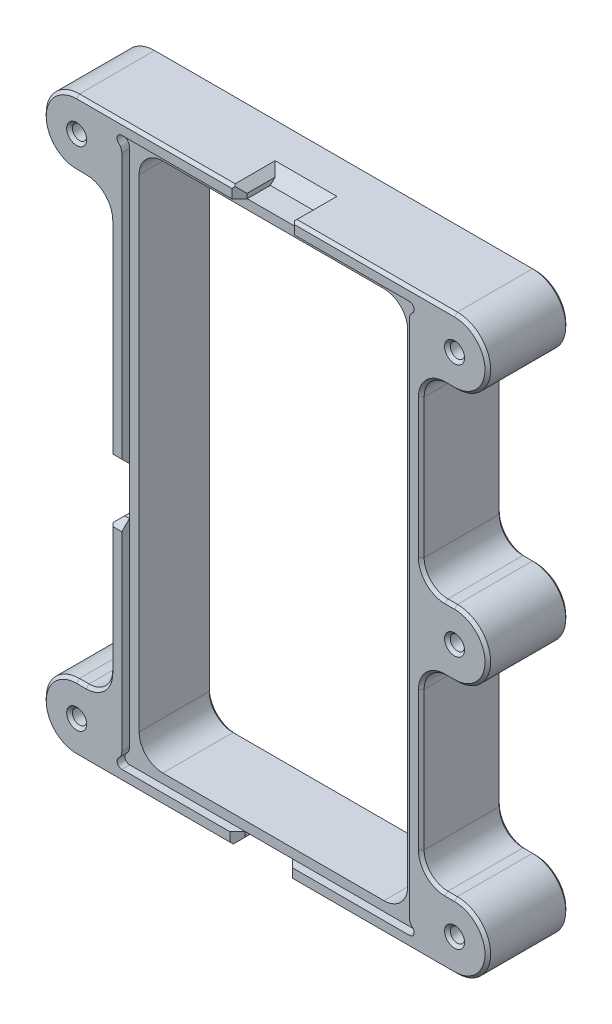
SolidWorks part; units mm, degrees
ref_plane "Top Plane" through (0, 0, 0) normal (0, 0, 1) x (1, 0, 0)
ref_plane "Right Plane" through (0, 0, 0) normal (0, 1, 0) x (1, 0, 0)
ref_plane "Front Plane" through (0, 0, 0) normal (1, 0, 0) x (0, 0, -1)
ref_plane "Plane1" through (60, 0, 0.0102) normal (0, 1, 0) x (1, 0, 0)
sketch "Sketch2" plane through (0, 0, 0) normal (0, 0, 1) x (1, 0, 0)
  line L4 (62.75, 2.75) -> (-2.75, 2.75)
  line L5 (-2.75, -11.25) -> (-2.75, -103.75)
  line L6 (-2.75, -117.75) -> (62.75, -117.75)
  line L8 (-0.25, -115.25) -> (60.25, -115.25)
  line L9 (60.25, -115.25) -> (60.25, 0.25)
  line L10 (-0.25, 0.25) -> (-0.25, -115.25)
  line L11 (60.25, 0.25) -> (-0.25, 0.25)
  line L12 (-0.25, -115.25) -> (60.25, -115.25)
  line L13 (60.25, -115.25) -> (60.25, 0.25)
  line L14 (-0.25, 0.25) -> (-0.25, -115.25)
  line L15 (60.25, 0.25) -> (-0.25, 0.25)
  line L16 (-2.75, -57.5) -> (62.75, -57.5) construction
  line L17 (30, -117.75) -> (30, 2.75) construction
  line L18 (-2.75, -117.75) -> (-9.75, -117.75)
  line L19 (-9.75, -103.75) -> (-2.75, -103.75)
  line L20 (-9.75, -11.25) -> (-2.75, -11.25)
  line L21 (-2.75, 2.75) -> (-9.75, 2.75)
  line L22 (-2.75, 2.75) -> (-2.75, -117.75) construction
  line L23 (62.75, -117.75) -> (62.75, 2.75) construction
  line L24 (62.75, 2.75) -> (69.75, 2.75)
  line L25 (69.75, -11.25) -> (62.75, -11.25)
  line L26 (69.75, -103.75) -> (62.75, -103.75)
  line L27 (62.75, -117.75) -> (69.75, -117.75)
  line L28 (62.75, -11.25) -> (62.75, -50.5)
  line L29 (69.75, -64.5) -> (62.75, -64.5)
  line L30 (69.75, -50.5) -> (62.75, -50.5)
  line L31 (62.75, -64.5) -> (62.75, -103.75)
  arc A0 (-9.75, -103.75) -> (-9.75, -117.75) centre (-9.75, -110.75) ccw
  circle A1 centre (-9.75, -110.75) radius 1.5
  circle A2 centre (-9.75, -4.25) radius 1.5
  arc A3 (-9.75, -11.25) -> (-9.75, 2.75) centre (-9.75, -4.25) cw
  arc A4 (69.75, -11.25) -> (69.75, 2.75) centre (69.75, -4.25) ccw
  circle A5 centre (69.75, -4.25) radius 1.5
  circle A6 centre (69.75, -110.75) radius 1.5
  arc A7 (69.75, -103.75) -> (69.75, -117.75) centre (69.75, -110.75) cw
  arc A8 (69.75, -64.5) -> (69.75, -50.5) centre (69.75, -57.5) ccw
  circle A9 centre (69.75, -57.5) radius 1.5
  dimension "D3" = 14
  dimension "D4" = 3
  dimension "D1" = 0.25
  dimension "D2" = 2.5
extrude "Boss-Extrude1" add sketch "Sketch2" against normal blind 17 contours L29 A8 L30 L28 L25 A4 L24 L4 L21 A3 L20 L5 L19 A0 L18 L6 L27 A7 L26 L31 A9 A6 A5 L15 L13 L12 L14 A1 A2 region at (66.25, 1.2248, 0)
sketch "Sketch3" plane through (0, 0, -17) normal (0, 0, -1) x (-1, 0, 0)
  line L8 (-1.75, -113.25) -> (-1.75, -1.75)
  line L9 (-1.75, -1.75) -> (-58.25, -1.75)
  line L10 (-58.25, -113.25) -> (-1.75, -113.25)
  line L11 (-58.25, -1.75) -> (-58.25, -113.25)
  line L12 (-1.75, -113.25) -> (-1.75, -1.75)
  line L13 (-1.75, -1.75) -> (-58.25, -1.75)
  line L14 (-58.25, -113.25) -> (-1.75, -113.25)
  line L15 (-58.25, -1.75) -> (-58.25, -113.25)
  line M8 (-60.25, 0.25) -> (0.25, 0.25)
  line M9 (0.25, 0.25) -> (0.25, -115.25)
  line M10 (0.25, -115.25) -> (-60.25, -115.25)
  line M11 (-60.25, -115.25) -> (-60.25, 0.25)
  dimension "D1" = 2
extrude "Boss-Extrude2" add sketch "Sketch3" against normal up to surface (15.3597 mm away) contours L15 L13 L12 L14 M8 M11 M10 M9 region at (30, -1.0539, -17)
fillet "Fillet1" radius 5 4 edges at (1.75, -1.75, -9.3201) (58.25, -1.75, -9.3201) (1.75, -113.25, -9.3201) (58.25, -113.25, -9.3201)
fillet "Fillet2" radius 5 6 edges at (62.75, -50.5, -8.5) (62.75, -64.5, -8.5) (62.75, -103.75, -8.5) (62.75, -11.25, -8.5) (-2.75, -11.25, -8.5) (-2.75, -103.75, -8.5)
sketch "Sketch4" plane through (0, 0, 0) normal (0, 0, 1) x (1, 0, 0)
  line L0 (27.195, -107.298) -> (31.005, -107.298) construction
  line L1 (7.49, -67.267) -> (7.49, -63.457) construction
  line L2 (27.595, -7.802) -> (31.405, -7.802) construction
  line L3 (29.5, -7.802) -> (29.5, 0.25) construction
  line L4 (60.25, 0.25) -> (-0.25, 0.25) construction
  line L5 (29.1, -107.298) -> (29.1, -115.25) construction
  line L6 (-0.25, -115.25) -> (60.25, -115.25) construction
  line L7 (7.49, -65.362) -> (-0.25, -65.362) construction
  line L8 (-0.25, 0.25) -> (-0.25, -115.25) construction
  line L9 (69.75, -117.75) -> (-9.75, -117.75) construction
  line L10 (24.1, -115.25) -> (34.1, -115.25)
  line L11 (24.1, -115.25) -> (24.1, -117.75)
  line L12 (24.1, -117.75) -> (34.1, -117.75)
  line L13 (34.1, -115.25) -> (34.1, -117.75)
  line L14 (-2.75, -16.25) -> (-2.75, -98.75) construction
  line L15 (-2.75, -70.362) -> (-0.25, -70.362)
  line L16 (-2.75, -70.362) -> (-2.75, -60.362)
  line L17 (-2.75, -60.362) -> (-0.25, -60.362)
  line L18 (-0.25, -70.362) -> (-0.25, -60.362)
  line L19 (-9.75, 2.75) -> (69.75, 2.75) construction
  line L20 (24.5, 0.25) -> (34.5, 0.25)
  line L21 (24.5, 0.25) -> (24.5, 2.75)
  line L22 (24.5, 2.75) -> (34.5, 2.75)
  line L23 (34.5, 0.25) -> (34.5, 2.75)
  circle A0 centre (31.405, -7.802) radius 0.7 construction
  circle A1 centre (27.595, -7.802) radius 0.7 construction
  circle A2 centre (31.405, -7.802) radius 0.7
  circle A3 centre (27.595, -7.802) radius 0.7
  circle A4 centre (27.195, -107.298) radius 0.7 construction
  circle A5 centre (31.005, -107.298) radius 0.7 construction
  circle A6 centre (27.195, -107.298) radius 0.7
  circle A7 centre (31.005, -107.298) radius 0.7
  circle A8 centre (7.49, -67.267) radius 0.7 construction
  circle A9 centre (7.49, -63.457) radius 0.7 construction
  circle A10 centre (7.49, -67.267) radius 0.7
  circle A11 centre (7.49, -63.457) radius 0.7
  point P48 (0, 0)
  point P49 (0, 0)
  point P50 (0, 0)
  dimension "D1" = 10
extrude "Cut-Extrude1" cut sketch "Sketch4" against normal blind 6.5 contours L11 L10 L13 L12 | L16 L15 L18 L17 | L21 L20 L23 L22
chamfer "Chamfer1" distance 1.6 angle 45 6 edges at (24.5, 1.5, 0) (34.5, 1.5, 0) (-1.5, -60.362, 0) (-1.5, -70.362, 0) (34.1, -116.5, 0) (24.1, -116.5, 0)
chamfer "Chamfer2" distance 2.5 angle 45 3 edges at (29.5, 2.75, -6.5) (-2.75, -65.362, -6.5) (29.1, -117.75, -6.5)
sketch "Sketch5" plane through (0, 0, 0) normal (0, 0, 1) x (1, 0, 0)
  line L0 (-0.25, 0.25) -> (-0.25, -58.762) construction
  line L5 (-0.25, -71.962) -> (-0.25, -115.25) construction
  line L6 (60.25, -115.25) -> (60.25, 0.25) construction
  line L7 (60.25, 0.25) -> (36.1, 0.25) construction
  line L8 (-0.25, -115.25) -> (22.5, -115.25) construction
  circle A2 centre (-0.25, -0.75) radius 1
  circle A3 centre (-0.25, -114.25) radius 1
  circle A4 centre (60.25, -114.25) radius 1
  circle A5 centre (60.25, -0.75) radius 1
  point P16 (60.25, -2.3032)
  point P19 (-0.25, -112.0231)
  dimension "D1" = 2
extrude "Cut-Extrude2" cut sketch "Sketch5" against normal up to surface (1.6403 mm away) contours A3 | A4 | A5 | A2 up to face at (23.67, -59.0724, -1.6403)
fillet "Fillet3" radius 2 4 edges at (60.25, -113.25, -0.8201) (60.25, -1.75, -0.8201) (-0.25, -1.75, -0.8201) (-0.25, -113.25, -0.8201)
chamfer "Chamfer3" distance 0.6 angle 45 22 edges at (-16.75, -4.25, -17) (30, 2.75, -17) (-8.75, -11.25, -17) (76.75, -4.25, -17) (-4.2145, -12.7145, -17) (68.75, -11.25, -17) (-2.75, -57.5, -17) (64.2145, -12.7145, -17) (-4.2145, -102.2855, -17) (62.75, -30.875, -17) (-8.75, -103.75, -17) (64.2145, -49.0355, -17) (-16.75, -110.75, -17) (68.75, -50.5, -17) (30, -117.75, -17) (76.75, -57.5, -17) (76.75, -110.75, -17) (68.75, -64.5, -17) (68.75, -103.75, -17) (64.2145, -65.9645, -17) (64.2145, -102.2855, -17) (62.75, -84.125, -17)
chamfer "Chamfer4" distance 0.6 angle 45 25 edges at (6.575, 2.75, 0) (-16.75, -4.25, 0) (-8.75, -11.25, 0) (-4.2145, -12.7145, 0) (-2.75, -37.506, 0) (6.375, -117.75, 0) (-16.75, -110.75, 0) (-2.75, -85.356, 0) (-8.75, -103.75, 0) (-4.2145, -102.2855, 0) (52.925, 2.75, 0) (76.75, -4.25, 0) (68.75, -11.25, 0) (64.2145, -12.7145, 0) (62.75, -30.875, 0) (64.2145, -49.0355, 0) (68.75, -50.5, 0) (52.725, -117.75, 0) (76.75, -57.5, 0) (76.75, -110.75, 0) (68.75, -64.5, 0) (68.75, -103.75, 0) (64.2145, -65.9645, 0) (64.2145, -102.2855, 0) (62.75, -84.125, 0)
chamfer "Chamfer5" distance 1.5 angle 45 6 edges at (24.1, -117.75, -5.3) (34.1, -117.75, -5.3) (-2.75, -70.362, -5.3) (-2.75, -60.362, -5.3) (24.5, 2.75, -5.3) (34.5, 2.75, -5.3)
chamfer "Chamfer6" distance 0.6 angle 45 8 edges at (58.25, -57.5, -17) (56.7855, -111.7855, -17) (56.7855, -3.2145, -17) (30, -113.25, -17) (30, -1.75, -17) (3.2145, -111.7855, -17) (3.2145, -3.2145, -17) (1.75, -57.5, -17)
sketch "Sketch6" plane through (0, 0, -17) normal (0, 0, -1) x (-1, 0, 0)
  line L1 (-68.0179, -7.25) -> (-66.2859, -4.25)
  line L2 (-66.2859, -4.25) -> (-68.0179, -1.25)
  line L3 (-68.0179, -1.25) -> (-71.4821, -1.25)
  line L4 (-71.4821, -1.25) -> (-73.2141, -4.25)
  line L5 (-73.2141, -4.25) -> (-71.4821, -7.25)
  line L6 (-71.4821, -7.25) -> (-68.0179, -7.25)
  line L7 (6.2859, -4.25) -> (8.0179, -7.25)
  line L8 (8.0179, -7.25) -> (11.4821, -7.25)
  line L9 (11.4821, -7.25) -> (13.2141, -4.25)
  line L10 (13.2141, -4.25) -> (11.4821, -1.25)
  line L11 (11.4821, -1.25) -> (8.0179, -1.25)
  line L12 (8.0179, -1.25) -> (6.2859, -4.25)
  line L13 (6.2859, -110.75) -> (8.0179, -113.75)
  line L14 (8.0179, -113.75) -> (11.4821, -113.75)
  line L15 (11.4821, -113.75) -> (13.2141, -110.75)
  line L16 (13.2141, -110.75) -> (11.4821, -107.75)
  line L17 (11.4821, -107.75) -> (8.0179, -107.75)
  line L18 (8.0179, -107.75) -> (6.2859, -110.75)
  line L19 (-66.2859, -110.75) -> (-68.0179, -107.75)
  line L20 (-68.0179, -107.75) -> (-71.4821, -107.75)
  line L21 (-71.4821, -107.75) -> (-73.2141, -110.75)
  line L22 (-73.2141, -110.75) -> (-71.4821, -113.75)
  line L23 (-71.4821, -113.75) -> (-68.0179, -113.75)
  line L24 (-68.0179, -113.75) -> (-66.2859, -110.75)
  line L25 (-66.2859, -57.5) -> (-68.0179, -54.5)
  line L26 (-68.0179, -54.5) -> (-71.4821, -54.5)
  line L27 (-71.4821, -54.5) -> (-73.2141, -57.5)
  line L28 (-73.2141, -57.5) -> (-71.4821, -60.5)
  line L29 (-71.4821, -60.5) -> (-68.0179, -60.5)
  line L30 (-68.0179, -60.5) -> (-66.2859, -57.5)
  circle A0 centre (-69.75, -4.25) radius 3 construction
  circle A1 centre (9.75, -4.25) radius 3 construction
  circle A2 centre (9.75, -110.75) radius 3 construction
  circle A3 centre (-69.75, -110.75) radius 3 construction
  circle A4 centre (-69.75, -57.5) radius 3 construction
  circle M56 centre (-69.75, -57.5) radius 1.5
  circle M57 centre (-69.75, -110.75) radius 1.5
  circle M58 centre (-69.75, -4.25) radius 1.5
  circle M59 centre (9.75, -110.75) radius 1.5
  circle M60 centre (9.75, -4.25) radius 1.5
  dimension "D1" = 6
extrude "Cut-Extrude3" cut sketch "Sketch6" against normal blind 10 contours L17 L18 L13 L14 L15 L16 M59 | L23 L24 L19 L20 L21 L22 M57 | L29 L30 L25 L26 L27 L28 M56 | L5 L6 L1 L2 L3 L4 M58 | L11 L12 L7 L8 L9 L10 M60 | L13 L14 L15 L16 L17 L18 region at (69.75, -7.1583, -17) region at (-7.2313, -2.7958, -17) region at (-7.2313, -109.2958, -17) region at (67.2313, -112.2042, -17) region at (67.2313, -58.9542, -17)
chamfer "Chamfer7" distance 2 angle 45 5 edges at (-11.25, -4.25, -7) (68.25, -4.25, -7) (68.25, -57.5, -7) (-11.25, -110.75, -7) (68.25, -110.75, -7)
chamfer "Chamfer8" distance 0.6 angle 45 5 edges at (-8.25, -4.25, 0) (-8.25, -110.75, 0) (71.25, -110.75, 0) (71.25, -57.5, 0) (71.25, -4.25, 0)
